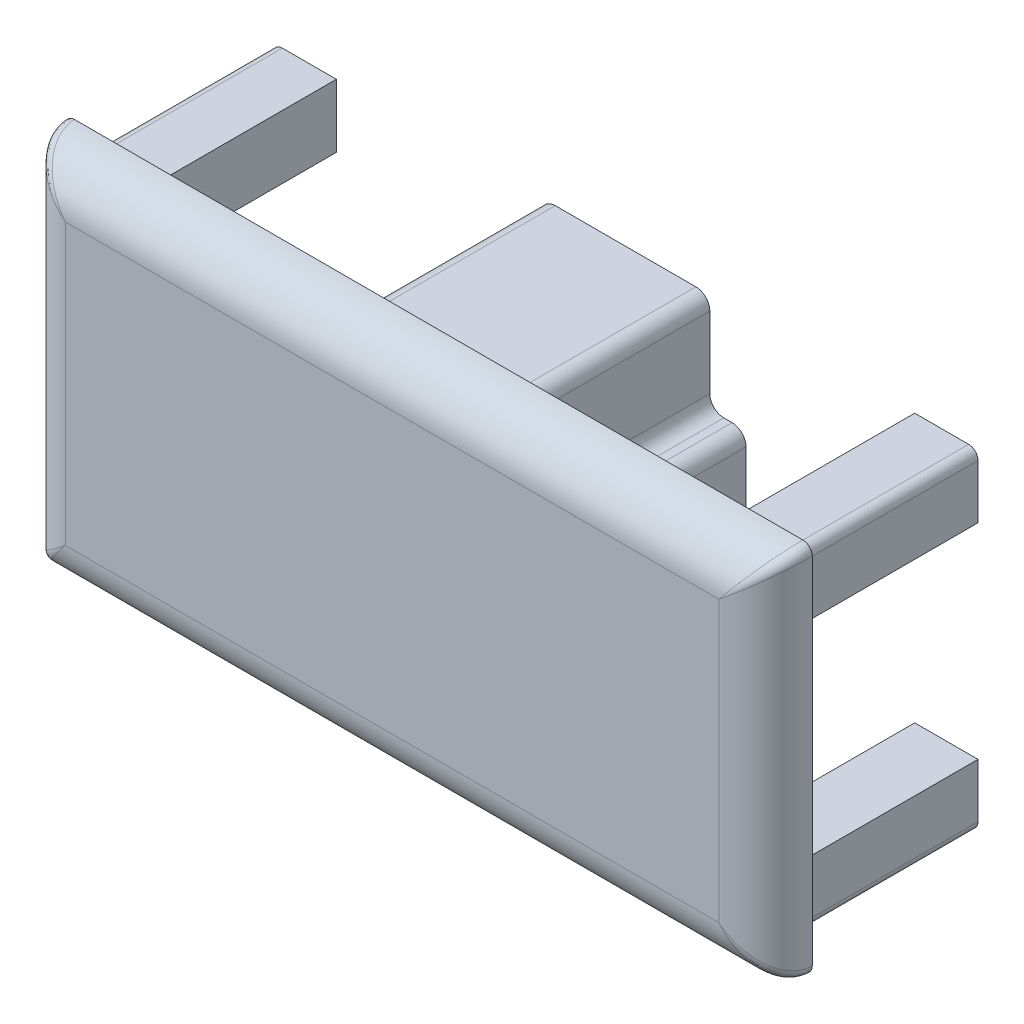
SolidWorks part; units mm, degrees
material "POLIURETAN (11671)"
ref_plane "Płaszczyzna przednia" through (0, 0, 0) normal (0, 0, 1) x (1, 0, 0)
ref_plane "Płaszczyzna górna" through (0, 0, 0) normal (0, 1, 0) x (1, 0, 0)
ref_plane "Płaszczyzna prawa" through (0, 0, 0) normal (1, 0, 0) x (0, 0, -1)
sketch "Szkic1" plane through (0, 0, 0) normal (0, 0, 1) x (1, 0, 0)
  line L0 (0, 20) -> (0, -20) construction
  line L1 (-51.8865, 0) -> (40, 0) construction
  line L4 (-40, -19) -> (-40, 19)
  line L7 (-40, -20) -> (0, 0) construction
  line L8 (-40, 20) -> (40, -20) construction
  line L13 (20, 20) -> (20, 0) construction
  line L15 (24, 20) -> (24, 15.5)
  line L16 (24, 15.5) -> (26.4714, 15.5)
  line L21 (16, 15.5) -> (13.5286, 15.5)
  line L23 (16, 20) -> (13.5286, 20)
  line L24 (16, 20) -> (16, 15.5)
  line L25 (16, 7.75) -> (24, 7.75)
  line L26 (13.5286, 15.5) -> (13.5286, 17.75)
  line L27 (26.4714, 15.5) -> (26.4714, 17.75)
  line L28 (-24, 20) -> (-24, 15.5)
  line L29 (-26.4714, 15.5) -> (-26.4714, 17.75)
  line L30 (-24, 15.5) -> (-26.4714, 15.5)
  line L31 (-13.5286, 15.5) -> (-13.5286, 17.75)
  line L32 (-16, 15.5) -> (-13.5286, 15.5)
  line L33 (-16, 20) -> (-16, 15.5)
  line L34 (-16, 7.75) -> (-24, 7.75)
  line L35 (20, -20) -> (20, 0) construction
  line L36 (-40, -20) -> (0, 0) construction
  line L37 (-40, 20) -> (40, -20) construction
  line L38 (30.9714, -17.75) -> (36.75, -17.75)
  line L39 (-16, -7.75) -> (-24, -7.75)
  line L40 (-16, -20) -> (-16, -15.5)
  line L41 (-16, -15.5) -> (-13.5286, -15.5)
  line L42 (-13.5286, -15.5) -> (-13.5286, -17.75)
  line L43 (-24, -15.5) -> (-26.4714, -15.5)
  line L44 (-26.4714, -15.5) -> (-26.4714, -17.75)
  line L45 (-24, -20) -> (-24, -15.5)
  line L46 (26.4714, -15.5) -> (26.4714, -17.75)
  line L47 (13.5286, -15.5) -> (13.5286, -17.75)
  line L48 (16, -7.75) -> (24, -7.75)
  line L49 (16, -20) -> (16, -15.5)
  line L50 (16, -15.5) -> (13.5286, -15.5)
  line L51 (24, -15.5) -> (26.4714, -15.5)
  line L52 (24, -20) -> (24, -15.5)
  line L53 (40, -20) -> (0, 20) construction
  line L54 (35.5, 6.4714) -> (37.75, 6.4714)
  line L55 (35.5, 4) -> (35.5, 6.4714)
  line L56 (40, 4) -> (35.5, 4)
  line L57 (40, -4) -> (35.5, -4)
  line L58 (35.5, -4) -> (35.5, -6.4714)
  line L59 (35.5, -6.4714) -> (37.75, -6.4714)
  line L60 (27.75, 4) -> (27.75, -4)
  line L61 (-35.5, -6.4714) -> (-37.75, -6.4714)
  line L62 (-37.75, -4) -> (-35.5, -4)
  line L63 (-35.5, -4) -> (-35.5, -6.4714)
  line L64 (-35.5, 4) -> (-35.5, 6.4714)
  line L65 (-35.5, 6.4714) -> (-37.75, 6.4714)
  line L66 (-37.75, 4) -> (-35.5, 4)
  line L67 (-27.75, 4) -> (-27.75, -4)
  line L68 (-37.75, 4) -> (-37.75, -4)
  line L69 (40, -4) -> (40, -19)
  line L70 (40, 19) -> (40, 4)
  line L71 (-39, -20) -> (-24, -20)
  line L72 (-16, -20) -> (16, -20)
  line L73 (24, -20) -> (39, -20)
  line L74 (13.5286, 20) -> (-16, 20)
  line L75 (-24, 20) -> (-39, 20)
  line L76 (24, 20) -> (39, 20)
  line L77 (10.5286, 7.0902) -> (11.4095, 7.0902)
  line L78 (-7.5286, -17.75) -> (7.5286, -17.75)
  line L79 (-9.0286, -16.25) -> (-9.0286, -8.5902)
  line L80 (-7.5286, 17.75) -> (7.5286, 17.75)
  line L81 (9.0286, -16.25) -> (9.0286, -8.5902)
  line L82 (-9.0286, -17.75) -> (9.0286, 17.75) construction
  line L83 (-9.0286, 17.75) -> (9.0286, -17.75) construction
  line L84 (-11.4095, -7.0902) -> (-10.5286, -7.0902)
  line L85 (-12.9095, -5.5902) -> (-12.9095, 5.5902)
  line L86 (-11.4095, 7.0902) -> (-10.5286, 7.0902)
  line L87 (12.9095, -5.5902) -> (12.9095, 5.5902)
  line L88 (-12.9095, -7.0902) -> (0, 0) construction
  line L89 (-12.9095, 7.0902) -> (12.9095, -7.0902) construction
  line L90 (-9.0286, 8.5902) -> (-9.0286, 16.25)
  line L91 (-9.0286, 4.5143) -> (-9.0286, 4.9587)
  line L92 (-9.0286, -4.9587) -> (-9.0286, -4.5143)
  line L93 (9.0286, 8.5902) -> (9.0286, 16.25)
  line L94 (10.5286, -7.0902) -> (11.4095, -7.0902)
  line L96 (0, 0) -> (12.9095, 7.0902) construction
  line L98 (37.75, -10.9714) -> (37.75, -16.75)
  line L99 (30.9714, 10.9714) -> (37.75, 10.9714)
  line L100 (30.9714, 10.9714) -> (30.9714, 17.75)
  line L101 (30.9714, 17.75) -> (36.75, 17.75)
  line L102 (37.75, 10.9714) -> (37.75, 16.75)
  line L103 (30.9714, 10.9714) -> (37.75, 17.75) construction
  line L104 (30.9714, 17.75) -> (37.75, 10.9714) construction
  line L105 (30.9714, -10.9714) -> (37.75, -10.9714)
  line L106 (30.9714, -10.9714) -> (30.9714, -17.75)
  line L107 (-30.9714, -10.9714) -> (-30.9714, -17.75)
  line L108 (-30.9714, -10.9714) -> (-37.75, -10.9714)
  line L109 (-37.75, -10.9714) -> (-37.75, -16.75)
  line L110 (-30.9714, -17.75) -> (-36.75, -17.75)
  line L111 (-30.9714, 17.75) -> (-36.75, 17.75)
  line L112 (-37.75, 10.9714) -> (-37.75, 16.75)
  line L113 (-30.9714, 10.9714) -> (-37.75, 10.9714)
  line L114 (-30.9714, 10.9714) -> (-30.9714, 17.75)
  line L115 (-31.9714, 16.75) -> (-36.75, 16.75)
  line L116 (-36.75, 11.9714) -> (-36.75, 16.75)
  line L117 (-31.9714, 11.9714) -> (-36.75, 11.9714)
  line L118 (-31.9714, 11.9714) -> (-31.9714, 16.75)
  line L119 (-31.9714, -11.9714) -> (-31.9714, -16.75)
  line L120 (-31.9714, -16.75) -> (-36.75, -16.75)
  line L121 (-36.75, -11.9714) -> (-36.75, -16.75)
  line L122 (-31.9714, -11.9714) -> (-36.75, -11.9714)
  line L123 (-7.5286, 16.75) -> (7.5286, 16.75)
  line L124 (8.0286, 8.5902) -> (8.0286, 16.25)
  line L125 (10.5286, 6.0902) -> (11.4095, 6.0902)
  line L126 (11.9095, -5.5902) -> (11.9095, 5.5902)
  line L127 (10.5286, -6.0902) -> (11.4095, -6.0902)
  line L128 (8.0286, -16.25) -> (8.0286, -8.5902)
  line L129 (-7.5286, -16.75) -> (7.5286, -16.75)
  line L130 (-8.0286, -16.25) -> (-8.0286, -8.5902)
  line L131 (-11.4095, -6.0902) -> (-10.5286, -6.0902)
  line L132 (-11.9095, -5.5902) -> (-11.9095, 5.5902)
  line L133 (-11.4095, 6.0902) -> (-10.5286, 6.0902)
  line L134 (-8.0286, 8.5902) -> (-8.0286, 16.25)
  line L135 (31.9714, -16.75) -> (36.75, -16.75)
  line L136 (36.75, -11.9714) -> (36.75, -16.75)
  line L137 (31.9714, -11.9714) -> (36.75, -11.9714)
  line L138 (31.9714, -11.9714) -> (31.9714, -16.75)
  line L139 (31.9714, 11.9714) -> (31.9714, 16.75)
  line L140 (31.9714, 16.75) -> (36.75, 16.75)
  line L141 (36.75, 11.9714) -> (36.75, 16.75)
  line L142 (31.9714, 11.9714) -> (36.75, 11.9714)
  circle A0 centre (-20, 0) radius 3.4
  circle A1 centre (20, 0) radius 3.4
  arc A2 (26.4714, 17.75) -> (28.7214, 15.5) centre (26.4714, 15.5) cw
  arc A3 (28.7214, 15.5) -> (24, 7.75) centre (20, 15.5) cw
  arc A4 (13.5286, 17.75) -> (11.2786, 15.5) centre (13.5286, 15.5) ccw
  arc A5 (11.2786, 15.5) -> (16, 7.75) centre (20, 15.5) ccw
  arc A6 (-26.4714, 17.75) -> (-28.7214, 15.5) centre (-26.4714, 15.5) ccw
  arc A7 (-13.5286, 17.75) -> (-11.2786, 15.5) centre (-13.5286, 15.5) cw
  arc A8 (-11.2786, 15.5) -> (-16, 7.75) centre (-20, 15.5) cw
  arc A9 (-28.7214, 15.5) -> (-24, 7.75) centre (-20, 15.5) ccw
  arc A10 (-28.7214, -15.5) -> (-24, -7.75) centre (-20, -15.5) cw
  arc A11 (-11.2786, -15.5) -> (-16, -7.75) centre (-20, -15.5) ccw
  arc A12 (-13.5286, -17.75) -> (-11.2786, -15.5) centre (-13.5286, -15.5) ccw
  arc A13 (-26.4714, -17.75) -> (-28.7214, -15.5) centre (-26.4714, -15.5) cw
  arc A14 (11.2786, -15.5) -> (16, -7.75) centre (20, -15.5) cw
  arc A15 (13.5286, -17.75) -> (11.2786, -15.5) centre (13.5286, -15.5) cw
  arc A16 (28.7214, -15.5) -> (24, -7.75) centre (20, -15.5) ccw
  arc A17 (26.4714, -17.75) -> (28.7214, -15.5) centre (26.4714, -15.5) ccw
  arc A18 (35.5, 8.7214) -> (27.75, 4) centre (35.5, 0) ccw
  arc A19 (37.75, 6.4714) -> (35.5, 8.7214) centre (35.5, 6.4714) ccw
  arc A20 (37.75, -6.4714) -> (35.5, -8.7214) centre (35.5, -6.4714) cw
  arc A21 (35.5, -8.7214) -> (27.75, -4) centre (35.5, 0) cw
  arc A22 (-35.5, -8.7214) -> (-27.75, -4) centre (-35.5, 0) ccw
  arc A23 (-37.75, -6.4714) -> (-35.5, -8.7214) centre (-35.5, -6.4714) ccw
  arc A24 (-37.75, 6.4714) -> (-35.5, 8.7214) centre (-35.5, 6.4714) cw
  arc A25 (-35.5, 8.7214) -> (-27.75, 4) centre (-35.5, 0) cw
  arc A26 (-10.5286, 7.0902) -> (-9.0286, 8.5902) centre (-10.5286, 8.5902) ccw
  arc A27 (-9.0286, -8.5902) -> (-10.5286, -7.0902) centre (-10.5286, -8.5902) ccw
  arc A28 (11.4095, -7.0902) -> (12.9095, -5.5902) centre (11.4095, -5.5902) ccw
  arc A29 (9.0286, -8.5902) -> (10.5286, -7.0902) centre (10.5286, -8.5902) cw
  arc A30 (7.5286, -17.75) -> (9.0286, -16.25) centre (7.5286, -16.25) ccw
  arc A31 (-7.5286, -17.75) -> (-9.0286, -16.25) centre (-7.5286, -16.25) cw
  arc A32 (-11.4095, -7.0902) -> (-12.9095, -5.5902) centre (-11.4095, -5.5902) cw
  arc A33 (-12.9095, 5.5902) -> (-11.4095, 7.0902) centre (-11.4095, 5.5902) cw
  arc A34 (-9.0286, 16.25) -> (-7.5286, 17.75) centre (-7.5286, 16.25) cw
  arc A35 (7.5286, 17.75) -> (9.0286, 16.25) centre (7.5286, 16.25) cw
  arc A36 (11.4095, 7.0902) -> (12.9095, 5.5902) centre (11.4095, 5.5902) cw
  arc A37 (10.5286, 7.0902) -> (9.0286, 8.5902) centre (10.5286, 8.5902) cw
  arc A38 (-40, 19) -> (-39, 20) centre (-39, 19) cw
  arc A39 (-39, -20) -> (-40, -19) centre (-39, -19) cw
  arc A40 (39, -20) -> (40, -19) centre (39, -19) ccw
  arc A41 (39, 20) -> (40, 19) centre (39, 19) cw
  arc A42 (36.75, 17.75) -> (37.75, 16.75) centre (36.75, 16.75) cw
  arc A43 (36.75, -17.75) -> (37.75, -16.75) centre (36.75, -16.75) ccw
  arc A44 (-36.75, -17.75) -> (-37.75, -16.75) centre (-36.75, -16.75) cw
  arc A45 (-36.75, 17.75) -> (-37.75, 16.75) centre (-36.75, 16.75) ccw
  arc A46 (-36.75, 16.75) -> (-36.75, 16.75) centre (-36.75, 16.75) ccw
  circle A47 centre (-20, 0) radius 2.4
  arc A48 (-36.75, -16.75) -> (-36.75, -16.75) centre (-36.75, -16.75) cw
  arc A49 (7.5286, 16.75) -> (8.0286, 16.25) centre (7.5286, 16.25) cw
  arc A50 (10.5286, 6.0902) -> (8.0286, 8.5902) centre (10.5286, 8.5902) cw
  arc A51 (11.4095, 6.0902) -> (11.9095, 5.5902) centre (11.4095, 5.5902) cw
  arc A52 (11.4095, -6.0902) -> (11.9095, -5.5902) centre (11.4095, -5.5902) ccw
  arc A53 (8.0286, -8.5902) -> (10.5286, -6.0902) centre (10.5286, -8.5902) cw
  arc A54 (7.5286, -16.75) -> (8.0286, -16.25) centre (7.5286, -16.25) ccw
  arc A55 (-7.5286, -16.75) -> (-8.0286, -16.25) centre (-7.5286, -16.25) cw
  arc A56 (-8.0286, -8.5902) -> (-10.5286, -6.0902) centre (-10.5286, -8.5902) ccw
  arc A57 (-11.4095, -6.0902) -> (-11.9095, -5.5902) centre (-11.4095, -5.5902) cw
  arc A58 (-11.9095, 5.5902) -> (-11.4095, 6.0902) centre (-11.4095, 5.5902) cw
  arc A59 (-10.5286, 6.0902) -> (-8.0286, 8.5902) centre (-10.5286, 8.5902) ccw
  arc A60 (-8.0286, 16.25) -> (-7.5286, 16.75) centre (-7.5286, 16.25) cw
  arc A61 (36.75, -16.75) -> (36.75, -16.75) centre (36.75, -16.75) ccw
  circle A62 centre (20, 0) radius 2.4
  arc A63 (36.75, 16.75) -> (36.75, 16.75) centre (36.75, 16.75) cw
  point P5 (0, 0)
  point P17 (0, 0)
  point P30 (24, 17.75)
  point P108 (0, 0)
  point P124 (-9.0286, 7.0902)
  point P132 (9.0286, -7.0902)
  point P156 (9.0286, 7.0902)
  point P161 (40, 20)
  point P162 (34.3607, 14.3607)
  dimension "D4" = 6.8
  dimension "D5" = 12.25
  dimension "D9" = 11
  dimension "D11" = 1.5
  dimension "D12" = 1
  dimension "D16" = 1
  dimension "D1" = 80
  dimension "D2" = 40
  dimension "D3" = 40
  dimension "D6" = 2.25
  dimension "D7" = 8
  dimension "D8" = 4.5
  dimension "D10" = 14.1804
  dimension "D13" = 2.25
  dimension "D14" = 2.25
  dimension "D15" = 2.25
  dimension "D17" = 1
extrude "Dodanie-wyciągnięcie1" add sketch "Szkic1" along normal blind 20 contours L111 A45 L112 L113 L114 L118 L117 L116 L115 | A0 A47 | A44 L110 L107 L108 L109 L122 L119 L120 L121 | L77 A37 L93 A35 L80 A34 L90 A26 L86 A33 L85 A32 L84 A27 L79 A31 L78 A30 L81 A29 L94 A28 L87 A36 L134 A60 L123 A49 L124 A50 L125 A51 L126 A52 L127 A53 L128 A54 L129 A55 L130 A56 L131 A57 L132 A58 L133 A59 | A62 | A42 L101 L100 L99 L102 L142 L139 L140 L141 | L38 A43 L98 L105 L106 L138 L137 L136 L135 | A1 region at (31.0672, -14.3607, 0) region at (10.9691, 6.6512, 0) region at (31.0672, 14.3607, 0) region at (-31.0672, -14.3607, 0) region at (-31.0672, 14.3607, 0) region at (-23.3038, 0, 0) region at (20, 0, 0)
sketch "Szkic2" plane through (0, 0, 20) normal (0, 0, 1) x (1, 0, 0)
  line L1 (-40, -20) -> (40, -20)
  line L2 (-40, -20) -> (-40, 20)
  line L3 (-40, 20) -> (40, 20)
  line L4 (40, -20) -> (40, 20)
  line L5 (-40, -20) -> (40, 20) construction
  line L6 (-40, 20) -> (40, -20) construction
  point P0 (0, 0)
extrude "Dodanie-wyciągnięcie2" add sketch "Szkic2" along normal blind 5
fillet "Zaokrąglenie1" radius 1 4 edges at (-40, 20, 22.5) (40, 20, 22.5) (40, -20, 22.5) (-40, -20, 22.5)
fillet "Zaokrąglenie2" radius 5 8 edges at (39.7071, 19.7071, 25) (40, 0, 25) (39.7071, -19.7071, 25) (0, -20, 25) (-39.7071, -19.7071, 25) (-40, 0, 25) (-39.7071, 19.7071, 25) (0, 20, 25)
